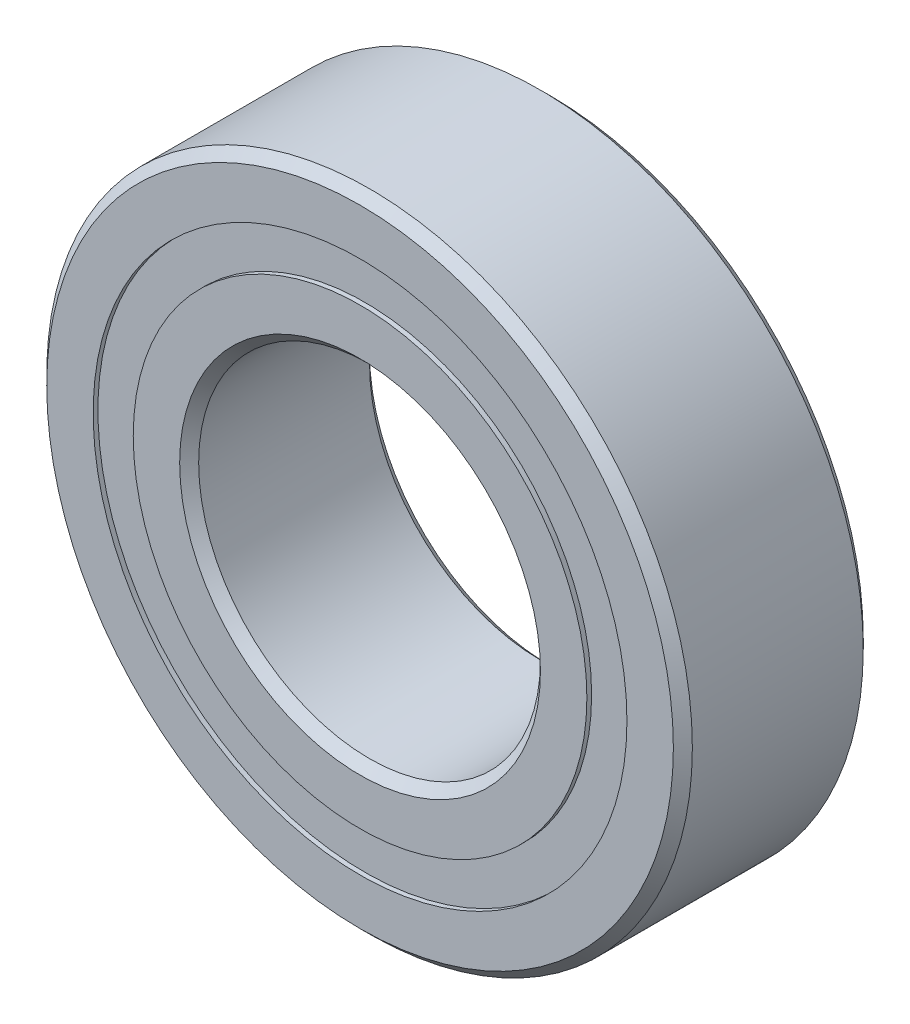
SolidWorks part; units mm, degrees
ref_plane "Front Plane" through (0, 0, 0) normal (0, 0, 1) x (1, 0, 0)
ref_plane "Top Plane" through (0, 0, 0) normal (0, 1, 0) x (1, 0, 0)
ref_plane "Right Plane" through (0, 0, 0) normal (1, 0, 0) x (0, 0, -1)
sketch "Sketch1" plane through (0, 0, 0) normal (1, 0, 0) x (0, 0, -1)
  line L0 (-2.5, 0) -> (2.5, 0) construction
  line L1 (0, 8.5) -> (0, -8.5) construction
  line L2 (2.25, 8.5) -> (-2.25, 8.5)
  line L3 (-2.25, 8.5) -> (-2.5, 8.25)
  line L4 (-2.5, 8.25) -> (-2.5, 7.0275)
  line L5 (-2.5, 7.0275) -> (-1.1111, 7.0275)
  line L6 (2.5, 7.0275) -> (1.1111, 7.0275)
  line L7 (2.5, 8.25) -> (2.5, 7.0275)
  line L8 (2.25, 8.5) -> (2.5, 8.25)
  line L9 (0, 8.5) -> (0, 6.5) construction
  line L10 (0, 6.5) -> (0, 4.5) construction
  arc A0 (-1.1111, 7.0275) -> (1.1111, 7.0275) centre (0, 6.5) cw
  point P14 (0, 4.5)
  dimension "Width" = 5
  dimension "OD" = 17
  dimension "D1" = 45
  dimension "D2" = 0.25
  dimension "Shaft Dia" = 9
  dimension "D3" = 2.2222
  dimension "D4" = 0.5275
revolve "Revolve1" add sketch "Sketch1" angle 360 about L0
sketch "Sketch3" plane through (0, 0, 0) normal (1, 0, 0) x (0, 0, -1)
  line L0 (-2.5, 5.9725) -> (-1.1111, 5.9725)
  line L1 (0, 8.5) -> (0, -8.5) construction
  line L2 (-2.5, 8.25) -> (-2.5, 7.0275) construction
  line L3 (-2.5, 5.9725) -> (-2.5, 4.75)
  line L4 (-2.25, 8.5) -> (-2.5, 8.25) construction
  line L5 (-2.5, 4.75) -> (-2.25, 4.5)
  line L6 (-2.25, 4.5) -> (2.25, 4.5)
  line L7 (2.25, 8.5) -> (2.25, -8.5) construction
  line L8 (2.25, 4.5) -> (2.5, 4.75)
  line L9 (2.5, -8.25) -> (2.5, 8.25) construction
  line L10 (2.5, 4.75) -> (2.5, 5.9725)
  line L11 (2.5, 5.9725) -> (1.1111, 5.9725)
  line L13 (2.25, 8.5) -> (2.5, 8.25) construction
  arc A0 (1.1111, 7.0275) -> (-1.1111, 7.0275) centre (0, 6.5) ccw construction
  arc A1 (1.1111, 5.9725) -> (-1.1111, 5.9725) centre (0, 6.5) cw
revolve "Revolve3" add sketch "Sketch3" angle 360 about L0
sketch "Sketch4" plane through (0, 0, 0) normal (1, 0, 0) x (0, 0, -1)
  line L0 (-1.23, 6.5) -> (1.23, 6.5)
  arc A2 (-1.23, 6.5) -> (1.23, 6.5) centre (0, 6.5) cw
  arc A3 (1.1111, 7.0275) -> (-1.1111, 7.0275) centre (0, 6.5) ccw construction
revolve "Revolve4" add sketch "Sketch4" angle 360 about L0
ref_axis "Axis1" through (0, 0, -2.5) along (0, 0, 1)
pattern_circular "CirPattern1" count 12 every 30 about axis through (0, 0, -2.5) along (0, 0, 1) of bodies 104
sketch "Sketch5" plane through (0, 0, 0) normal (1, 0, 0) x (0, 0, -1)
  line L0 (-2.5, 7.0275) -> (-1.1111, 7.0275) construction
  line L1 (-2.375, 7.0275) -> (-1.23, 7.0275)
  line L2 (-2.375, 7.0275) -> (-2.375, 5.9725)
  line L3 (-2.375, 5.9725) -> (-1.23, 5.9725)
  line L4 (-1.23, 7.0275) -> (-1.23, 5.9725)
  line L5 (-2.5, 5.9725) -> (-1.1111, 5.9725) construction
  line L6 (2.5, 7.0275) -> (1.1111, 7.0275) construction
  line L7 (2.375, 7.0275) -> (1.23, 7.0275)
  line L8 (2.375, 7.0275) -> (2.375, 5.9725)
  line L9 (2.375, 5.9725) -> (1.23, 5.9725)
  line L10 (1.23, 7.0275) -> (1.23, 5.9725)
  line L11 (2.5, 5.9725) -> (1.1111, 5.9725) construction
  line L12 (-2.25, 8.5) -> (-2.5, 8.25) construction
  point P18 (-2.375, 8.375)
revolve "Revolve5" add sketch "Sketch5" angle 360 about L0
sketch "Sketch6" plane through (0, 0, 0) normal (1, 0, 0) x (0, 0, -1)
  line L0 (2.5, 0) -> (-2.5, 0) construction
  line L1 (2.5, 7.0275) -> (1.4, 7.0275)
  line L2 (2.5, 7.0275) -> (2.5, 9.5)
  line L3 (2.5, 9.5) -> (1.4, 9.5)
  line L4 (1.4, 7.0275) -> (1.4, 9.5)
  dimension "Th" = 1.1
  dimension "Flange OD" = 19
revolve "Revolve6" [suppressed] add sketch "Sketch6" angle 360 about L0
equation "\"D2@Sketch1\" = \"Width@Sketch1\"*.05"
equation "\"D3@Sketch1\" = \"Width@Sketch1\"/2.25"
equation "\"D4@Sketch1\" = (((\"OD@Sketch1\"-\"Width@Sketch1\")/2)/3.25)/3.5"
equation "\"D2@CirPattern1\" = 360/\"Balls@CirPattern1\""
